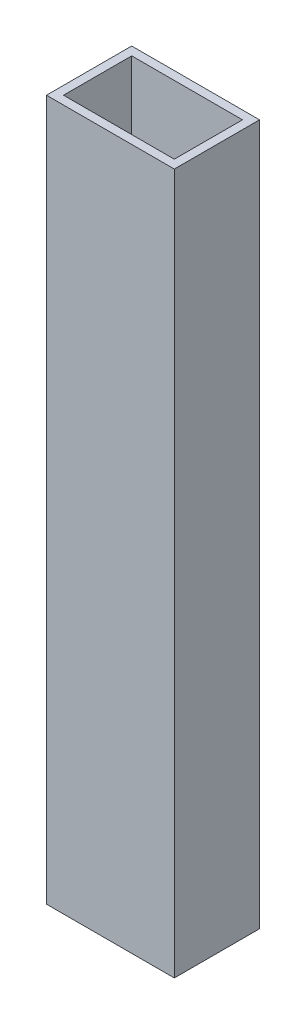
SolidWorks part; units mm, degrees
ref_plane "Front Plane" through (0, 0, 0) normal (0, 0, 1) x (1, 0, 0)
ref_plane "Top Plane" through (0, 0, 0) normal (0, 1, 0) x (1, 0, 0)
ref_plane "Right Plane" through (0, 0, 0) normal (1, 0, 0) x (0, 0, -1)
sketch "Sketch1" plane through (0, 0, 0) normal (0, 1, 0) x (1, 0, 0)
  line L1 (-3.75, -2.5) -> (3.75, -2.5)
  line L2 (-3.75, -2.5) -> (-3.75, 2.5)
  line L3 (-3.75, 2.5) -> (3.75, 2.5)
  line L4 (3.75, -2.5) -> (3.75, 2.5)
  line L5 (-3.75, -2.5) -> (3.75, 2.5) construction
  line L6 (-3.75, 2.5) -> (3.75, -2.5) construction
  line L11 (-3.25, 2) -> (3.25, 2)
  line L12 (-3.25, 2) -> (-3.25, -2)
  line L13 (-3.25, -2) -> (3.25, -2)
  line L14 (3.25, 2) -> (3.25, -2)
  line L15 (-3.25, 2) -> (3.25, -2) construction
  line L16 (-3.25, -2) -> (3.25, 2) construction
  point P0 (0, 0)
  point P6 (0, 0)
  point P7 (0, 0)
  dimension "D1" = 5
  dimension "D2" = 7.5
  dimension "D3" = 4
  dimension "D4" = 6.5
extrude "Boss-Extrude1" add sketch "Sketch1" along normal blind 41.1
sketch "Sketch2" plane through (-3.75, 0, 0) normal (-1, 0, 0) x (0, 0, 1)
  line L0 (-2.5, 41.1) -> (-2.5, 0) construction
  line L1 (-1.25, 1) -> (1.25, 1)
  line L2 (-1.25, 1) -> (-1.25, 3.5)
  line L3 (-1.25, 3.5) -> (1.25, 3.5)
  line L4 (1.25, 1) -> (1.25, 3.5)
  line L5 (-1.25, 1) -> (1.25, 3.5) construction
  line L6 (-1.25, 3.5) -> (1.25, 1) construction
  line L7 (-2.5, 0) -> (2.5, 0) construction
  point P0 (0, 2.25)
  dimension "D1" = 2.5
  dimension "D2" = 2.5
  dimension "D3" = 2.5
  dimension "D4" = 1
extrude "Cut-Extrude1" cut sketch "Sketch2" against normal up to surface (0.5 mm away) and the other way through all up to face at (-3.25, 20.55, 0)
scale "Scale1" scale about centroid uniform scaling yes scale factor 6
